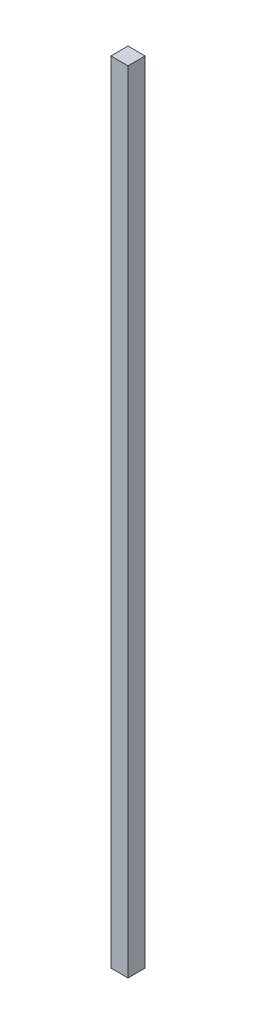
SolidWorks part; units mm, degrees
ref_plane "Plan de face" through (0, 0, 0) normal (0, 0, 1) x (1, 0, 0)
ref_plane "Plan de dessus" through (0, 0, 0) normal (0, 1, 0) x (1, 0, 0)
ref_plane "Plan de droite" through (0, 0, 0) normal (1, 0, 0) x (0, 0, -1)
sketch "Esquisse1" plane through (0, 0, 0) normal (0, 0, 1) x (1, 0, 0)
  line L1 (-40.4476, 31.9643) -> (-30.4476, 31.9643)
  line L2 (-40.4476, 31.9643) -> (-40.4476, -428.0357)
  line L3 (-40.4476, -428.0357) -> (-30.4476, -428.0357)
  line L4 (-30.4476, 31.9643) -> (-30.4476, -428.0357)
  dimension "D1" = 10
  dimension "D2" = 460
extrude "Boss.-Extru.1" add sketch "Esquisse1" along normal blind 10
equation "\"D2@Esquisse1\" = \"ProfondeurBoite\""
equation "\"EpaisseurPlaque\"= 3"
equation "\"ProfondeurBoite\"=460"
equation "\"LongueurSyphon\"=170"
equation "\"LargeurSyphon\"=120"
equation "\"HauteurCoteDroit\"= 490"
equation "\"HauteurCoteGauche\"= 540"
equation "\"HauteurSolSyphon\"= 300"
equation "\"HauteurSyphon\"=\"HauteurCoteGauche\"-\"HauteurSolSyphon\""
equation "\"LargeurDroite\"=10"
equation "\"LargeurGauche\"=150"
equation "\"LargeurBoite\"= \"LargeurDroite\" + \"LargeurGauche\" + \"LargeurSyphon\""
